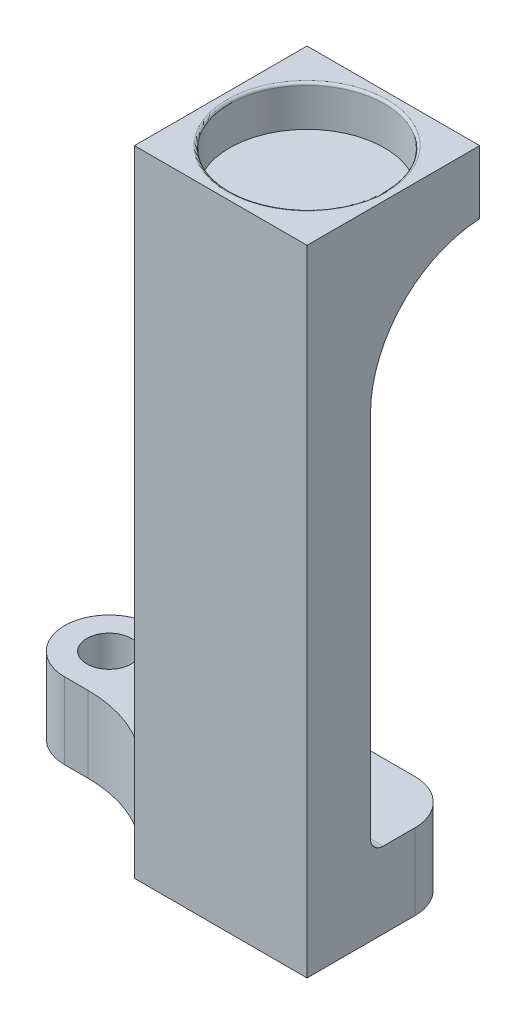
SolidWorks part; units mm, degrees
ref_plane "Front Plane" through (0, 0, 0) normal (0, 0, 1) x (1, 0, 0)
ref_plane "Top Plane" through (0, 0, 0) normal (0, 1, 0) x (1, 0, 0)
ref_plane "Right Plane" through (0, 0, 0) normal (1, 0, 0) x (0, 0, -1)
sketch "Sketch1" plane through (0, 0, 0) normal (0, 1, 0) x (1, 0, 0)
  line L1 (-6.8, 6.8) -> (6.8, 6.8)
  line L2 (-6.8, 6.8) -> (-6.8, -6.8)
  line L3 (-6.8, -6.8) -> (6.8, -6.8)
  line L4 (6.8, 6.8) -> (6.8, -6.8)
  line L5 (-6.8, 6.8) -> (6.8, -6.8) construction
  line L6 (-6.8, -6.8) -> (6.8, 6.8) construction
  point P0 (0, 0)
  dimension "D1" = 13.6
  dimension "D2" = 13.6
extrude "Boss-Extrude1" add sketch "Sketch1" along normal blind 5
sketch "Sketch2" plane through (0, 5, 0) normal (0, 1, 0) x (1, 0, 0)
  circle A0 centre (0, 0) radius 6.1
  dimension "D1" = 12.2
extrude "Cut-Extrude1" cut sketch "Sketch2" against normal blind 3.2
sketch "Sketch3" plane through (0, 0, 0) normal (0, -1, 0) x (1, 0, 0)
  line L0 (6.8, 6.8) -> (6.8, -6.8) construction
  line L1 (-6.8, 6.8) -> (6.8, 6.8)
  line L2 (-6.8, 6.8) -> (-6.8, 1.8)
  line L3 (-6.8, 1.8) -> (6.8, 1.8)
  line L4 (6.8, 6.8) -> (6.8, 1.8)
  dimension "D1" = 5
extrude "Boss-Extrude2" add sketch "Sketch3" along normal blind 45
sketch "Sketch4" plane through (0, 1.8, 0) normal (0, 1, 0) x (1, 0, 0)
  point P0 (0, 0)
fillet "Fillet1" radius 0.2 1 edges at (0, 5, 6.1)
fillet "Fillet2" radius 9 1 edges at (0, 0, 1.8)
sketch "Sketch10" plane through (0, 0, 1.8) normal (0, 0, -1) x (-1, 0, 0)
  line L1 (-6.8, -45) -> (20.8, -45)
  line L2 (-6.8, -45) -> (-6.8, -39)
  line L3 (-6.8, -39) -> (20.8, -39)
  line L4 (20.8, -45) -> (20.8, -39)
  dimension "D1" = 6
  dimension "D2" = 27.6
extrude "Boss-Extrude5" add sketch "Sketch10" along normal blind 7
sketch "Sketch11" plane through (0, -39, 0) normal (0, 1, 0) x (1, 0, 0)
  line L0 (-6.8, -1.8) -> (-6.8, 5.2) construction
  line L1 (-20.8, 5.2) -> (6.8, 5.2) construction
  line L2 (-6.8, 1.7) -> (-10.3, 1.7) construction
  line L3 (-10.3, 1.7) -> (-13.8, 1.7) construction
  line L4 (-17.3, 1.7) -> (-20.8, 1.7) construction
  line L5 (-20.8, 5.2) -> (-20.8, -1.8) construction
  line L6 (-13.8, 1.7) -> (-17.3, 1.7) construction
  circle A0 centre (-10.3, 1.7) radius 1.75
  circle A1 centre (-17.3, 1.7) radius 1.75
  dimension "D1" = 3.5
  dimension "D2" = 3.5
extrude "Cut-Extrude4" cut sketch "Sketch11" against normal through all
sketch "Sketch12" plane through (0, -39, 0) normal (0, 1, 0) x (1, 0, 0)
  line L0 (-10.3, 3.45) -> (-10.3, -0.05)
  circle A0 centre (-10.3, 1.7) radius 1.75
  point P4 (-10.3, 1.7)
fillet "Fillet3" radius 10 1 edges at (-6.8, -42, 1.8)
fillet "Fillet4" radius 3.5 3 edges at (-20.8, -42, 1.8) (-20.8, -42, -5.2) (6.8, -42, -5.2)
fillet "Fillet5" radius 1 2 edges at (-6.8, -39, 4.3) (0, -39, 1.8)
mirror "Mirror1" [suppressed] of bodies 109
delete or keep bodies "Body-Delete/Keep 1" [suppressed] type delete bodies bodies 109
